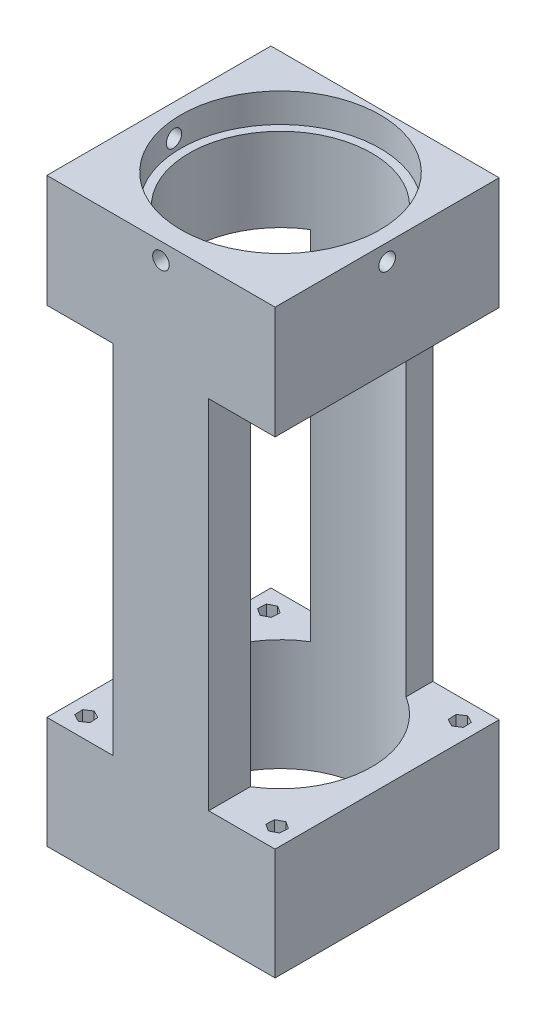
SolidWorks part; units mm, degrees
ref_plane "Front" through (0, 0, 0) normal (0, 0, 1) x (1, 0, 0)
ref_plane "Top" through (0, 0, 0) normal (0, 1, 0) x (1, 0, 0)
ref_plane "Right" through (0, 0, 0) normal (1, 0, 0) x (0, 0, -1)
sketch "草图1" plane through (0, 0, 0) normal (0, 0, 1) x (1, 0, 0)
  line L0 (-100, -70) -> (100, -70) construction
  line L1 (27.5, 70) -> (-27.5, 70)
  line L2 (27.5, 70) -> (27.5, -70)
  line L3 (27.5, -70) -> (-27.5, -70)
  line L4 (-27.5, 70) -> (-27.5, -70)
  line L5 (27.5, 70) -> (-27.5, -70) construction
  line L6 (27.5, -70) -> (-27.5, 70) construction
  point P0 (0, 0)
  dimension "D1" = 55
extrude "凸台-拉伸1" add sketch "草图1" along normal blind 54
sketch "草图2" plane through (0, 70, 0) normal (0, 1, 0) x (1, 0, 0)
  line L0 (27.5, 0) -> (-27.5, 0) construction
  circle A0 centre (0, -25.2) radius 22
  dimension "D1" = 44
  dimension "D2" = 25.2
extrude "切除-拉伸1" cut sketch "草图2" against normal through all contours A0
sketch "草图3" plane through (0, 0, 54) normal (0, 0, 1) x (1, 0, 0)
  line L1 (27.5, -70) -> (27.5, 70) construction
  line L3 (27.5, -43.1) -> (27.5, 42.9)
  line L4 (27.5, -43.1) -> (11.5, -43.1)
  line L5 (11.5, -43.1) -> (11.5, 42.9)
  line L6 (11.5, 42.9) -> (27.5, 42.9)
  line L7 (-27.5, -70) -> (27.5, -70) construction
  point P0 (19.5, -43.1)
  dimension "D1" = 86
  dimension "D2" = 26.9
  dimension "D3" = 16
extrude "切除-拉伸2" cut sketch "草图3" against normal up to surface (54 mm away)
mirror "镜向1" about plane through (0, 0, 0) normal (1, 0, 0) of "切除-拉伸2"
sketch "草图4" plane through (0, 70, 0) normal (0, 1, 0) x (1, 0, 0)
  circle A0 centre (0, -25.2) radius 24
  dimension "D1" = 48
extrude "切除-拉伸3" cut sketch "草图4" against normal blind 7
sketch "草图5" plane through (27.5, 0, 0) normal (1, 0, 0) x (0, 0, -1)
  line L0 (-54, 70) -> (0, 70) construction
  circle A0 centre (-27, 66) radius 2
  point P5 (-27, 70)
  dimension "D1" = 4
  dimension "D2" = 4
extrude "切除-拉伸4" cut sketch "草图5" against normal through all
sketch "草图6" plane through (0, 0, 54) normal (0, 0, 1) x (1, 0, 0)
  line L0 (27.5, 70) -> (-27.5, 70) construction
  circle A0 centre (0, 66) radius 2
  dimension "D1" = 4
  dimension "D2" = 4
extrude "切除-拉伸5" cut sketch "草图6" against normal blind 20
sketch "草图7" plane through (0, -43.1, 0) normal (0, 1, 0) x (1, 0, 0)
  line L0 (-11.5, -54) -> (-27.5, -54) construction
  line L1 (-24.7979, -48.0776) -> (-24.6978, -50.0958)
  line L2 (-24.6978, -50.0958) -> (-22.8999, -51.0182)
  line L3 (-22.8999, -51.0182) -> (-21.2021, -49.9224)
  line L4 (-21.2021, -49.9224) -> (-21.3022, -47.9042)
  line L5 (-21.3022, -47.9042) -> (-23.1001, -46.9818)
  line L6 (-23.1001, -46.9818) -> (-24.7979, -48.0776)
  line L7 (-27.5, 0) -> (-27.5, -54) construction
  circle A0 centre (-23, -49) radius 1.75 construction
  point P1 (-21.014, -45.6885)
  dimension "D1" = 3.5
  dimension "D2" = 5
  dimension "D3" = 4.5
extrude "切除-拉伸6" cut sketch "草图7" against normal blind 3
sketch "草图8" plane through (0, -46.1, 0) normal (0, 1, 0) x (1, 0, 0)
  line L0 (-27.5, 0) -> (-27.5, -54) construction
  line L1 (-11.5, -54) -> (-27.5, -54) construction
  circle A0 centre (-23, -49) radius 1.6
  dimension "D1" = 3.2
  dimension "D2" = 4.5
  dimension "D3" = 5
extrude "切除-拉伸7" cut sketch "草图8" against normal through all
mirror "镜向2" about plane through (0, 0, 0) normal (1, 0, 0) of "切除-拉伸6", "切除-拉伸7"
ref_plane "基准面2" through (0, 0, 27) normal (0, 0, 1) x (1, 0, 0)
mirror "镜向3" about plane through (0, 0, 27) normal (0, 0, 1) of "镜向2"
